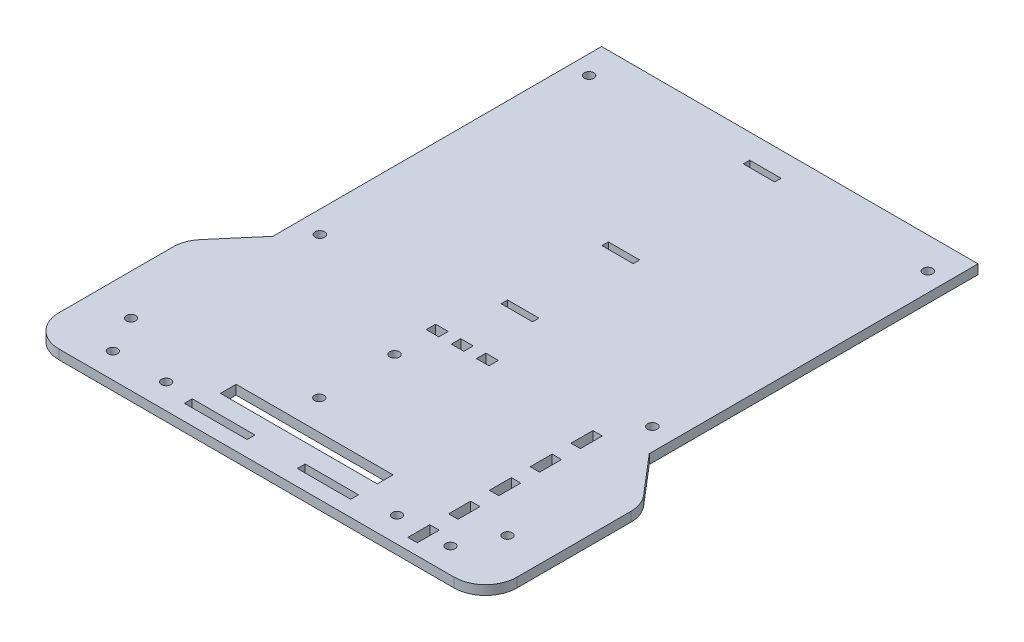
SolidWorks part; units mm, degrees
ref_plane "Front Plane" through (0, 0, 0) normal (0, 0, 1) x (1, 0, 0)
ref_plane "Top Plane" through (0, 0, 0) normal (0, 1, 0) x (1, 0, 0)
ref_plane "Right Plane" through (0, 0, 0) normal (1, 0, 0) x (0, 0, -1)
sketch "Sketch1" plane through (0, 0, 0) normal (0, 1, 0) x (1, 0, 0)
  line L0 (-73, -35) -> (-60, -19.8013)
  line L1 (60, -85) -> (-60, -85)
  line L2 (60, -19.8013) -> (60, 85)
  line L3 (60, 85) -> (-60, 85)
  line L4 (-60, -19.8013) -> (-60, 85)
  line L5 (60, -85) -> (-60, 85) construction
  line L6 (60, 85) -> (-60, -85) construction
  line L7 (0, 0) -> (0, -85) construction
  line L9 (-60, -85) -> (-73, -85)
  line L10 (-73, -35) -> (-73, -85)
  line L11 (60, -85) -> (73, -85)
  line L12 (73, -35) -> (73, -85)
  line L13 (73, -35) -> (60, -19.8013)
  point P0 (0, 0)
  dimension "D1" = 170
  dimension "D2" = 120
  dimension "D3" = 50
  dimension "D4" = 13
  dimension "D5" = 20
extrude "Boss-Extrude1" add sketch "Sketch1" along normal blind 3
sketch "Sketch2" plane through (0, 3, 0) normal (0, 1, 0) x (1, 0, 0)
  line L0 (0, 0) -> (0, 85) construction
  line L1 (60, 85) -> (-60, 85) construction
  line L2 (-60, 85) -> (-60, -19.8013) construction
  circle A0 centre (-53, -11.81) radius 1.525
  circle A1 centre (-54, 75) radius 1.525
  circle A2 centre (53, -11.81) radius 1.525
  circle A3 centre (54, 75) radius 1.525
  dimension "D1" = 10
  dimension "D2" = 3.05
  dimension "D3" = 6
  dimension "D4" = 3.05
  dimension "D5" = 7
  dimension "D6" = 86.81
extrude "Cut-Extrude1" cut sketch "Sketch2" against normal through all
sketch "Sketch3" plane through (0, 3, 0) normal (0, 1, 0) x (1, 0, 0)
  line L0 (-5, 32.14) -> (5, 32.14)
  line L1 (-5, 0.04) -> (5, 0.04)
  line L2 (-5, 0.04) -> (-5, -2.01)
  line L3 (-5, -2.01) -> (5, -2.01)
  line L4 (5, 0.04) -> (5, -2.01)
  line L5 (-5, 0.04) -> (5, -2.01) construction
  line L6 (-5, -2.01) -> (5, 0.04) construction
  line L7 (-5, 32.14) -> (-5, 30.09)
  line L8 (-5, 30.09) -> (5, 30.09)
  line L9 (5, 32.14) -> (5, 30.09)
  line L11 (-5, 77.24) -> (5, 77.24)
  line L12 (-5, 77.24) -> (-5, 75.19)
  line L13 (-5, 75.19) -> (5, 75.19)
  line L14 (-5, 64.24) -> (5, 64.24) [skipped]
  line L15 (-5, 64.24) -> (-5, 62.19) [skipped]
  line L16 (-5, 62.19) -> (5, 62.19) [skipped]
  line L17 (5, 64.24) -> (5, 62.19) [skipped]
  line L18 (5, 77.24) -> (5, 75.19)
  line L19 (-5, 77.24) -> (5, 75.19) construction
  line L20 (-5, 75.19) -> (5, 77.24) construction
  circle A0 centre (-53, -11.81) radius 1.525 construction
  point P0 (0, -0.985)
  point P8 (0, 76.215)
  dimension "D2" = 9.8
  dimension "D1" = 2.05
  dimension "D3" = 10
  dimension "D4" = 0
  dimension "D6" = 2.05
  dimension "D7" = 10
  dimension "D8" = 0
  dimension "D9" = 43.05
  dimension "D10" = 30.05
  dimension "D5" = 3
extrude "Cut-Extrude2" cut sketch "Sketch3" against normal through all
sketch "Sketch4" plane through (0, 3, 0) normal (0, 1, 0) x (1, 0, 0)
  line L0 (-73, -85) -> (73, -85) construction
  line L1 (-60, 85) -> (-60, -19.8013) construction
  line L2 (0, 0) -> (0, -85) construction
  circle A1 centre (-60, -65) radius 1.5
  circle A2 centre (-53.8153, -77) radius 1.5
  circle A3 centre (53.8153, -77) radius 1.5
  circle A4 centre (60, -65) radius 1.5
  dimension "D1" = 3
  dimension "D2" = 3
  dimension "D4" = 8
  dimension "D5" = 13.5
  dimension "D6" = 0
  dimension "D3" = 20
extrude "Cut-Extrude3" cut sketch "Sketch4" against normal blind 3
sketch "Sketch5" plane through (0, 3, 0) normal (0, 1, 0) x (1, 0, 0)
  line L0 (0, 0) -> (0, -85) construction
  line L2 (25, -71.5) -> (-25, -71.5)
  line L3 (25, -71.5) -> (25, -66.5)
  line L4 (25, -66.5) -> (-25, -66.5)
  line L5 (-25, -71.5) -> (-25, -66.5)
  line L6 (25, -71.5) -> (-25, -66.5) construction
  line L7 (-73, -85) -> (73, -85) construction
  line L8 (25, -66.5) -> (-25, -71.5) construction
  circle A0 centre (-36.8, -77) radius 1.5
  circle A1 centre (36.8, -77) radius 1.5
  point P0 (0, -69)
  dimension "D3" = 3
  dimension "D4" = 5.5
  dimension "D5" = 8
  dimension "D1" = 5
  dimension "D2" = 50
  dimension "D6" = 36.8
extrude "Cut-Extrude4" cut sketch "Sketch5" against normal blind 3
sketch "Sketch6" plane through (0, 3, 0) normal (0, 1, 0) x (1, 0, 0)
  line L0 (44.6365, -35.4032) -> (44.6365, -42.4032)
  line L7 (44.6365, -22.4032) -> (47.6365, -22.4032)
  line L8 (44.6365, -22.4032) -> (44.6365, -29.4032)
  line L9 (44.6365, -29.4032) -> (47.6365, -29.4032)
  line L10 (47.6365, -22.4032) -> (47.6365, -29.4032)
  line L11 (44.6365, -22.4032) -> (47.6365, -29.4032) construction
  line L12 (44.6365, -29.4032) -> (47.6365, -22.4032) construction
  line L13 (44.6365, -35.4032) -> (47.6365, -35.4032)
  line L14 (47.6365, -35.4032) -> (47.6365, -42.4032)
  line L15 (44.6365, -42.4032) -> (47.6365, -42.4032)
  line L16 (44.6365, -48.4032) -> (44.6365, -55.4032)
  line L17 (44.6365, -48.4032) -> (47.6365, -48.4032)
  line L18 (47.6365, -48.4032) -> (47.6365, -55.4032)
  line L19 (44.6365, -55.4032) -> (47.6365, -55.4032)
  line L20 (44.6365, -61.4032) -> (44.6365, -68.4032)
  line L21 (44.6365, -61.4032) -> (47.6365, -61.4032)
  line L22 (47.6365, -61.4032) -> (47.6365, -68.4032)
  line L23 (44.6365, -68.4032) -> (47.6365, -68.4032)
  line L24 (44.6365, -74.4032) -> (44.6365, -81.4032)
  line L25 (44.6365, -74.4032) -> (47.6365, -74.4032)
  line L26 (47.6365, -74.4032) -> (47.6365, -81.4032)
  line L27 (44.6365, -81.4032) -> (47.6365, -81.4032)
  line L29 (-9.793, -18.112) -> (-5.793, -18.112)
  line L30 (-9.793, -18.112) -> (-9.793, -21.112)
  line L31 (-9.793, -21.112) -> (-5.793, -21.112)
  line L32 (-5.793, -18.112) -> (-5.793, -21.112)
  line L33 (-9.793, -18.112) -> (-5.793, -21.112) construction
  line L34 (-9.793, -21.112) -> (-5.793, -18.112) construction
  line L35 (0.1365, -44.4032) -> (9.41, -44.4032) construction
  line L39 (-1.793, -18.1033) -> (2.207, -18.1033)
  line L40 (-1.793, -18.1033) -> (-1.793, -21.1033)
  line L41 (-1.793, -21.1033) -> (2.207, -21.1033)
  line L42 (2.207, -18.1033) -> (2.207, -21.1033)
  line L43 (-7.793, -19.612) -> (-7.793, -18.4227) construction
  line L44 (6.207, -18.1033) -> (10.207, -18.1033)
  line L45 (6.207, -18.1033) -> (6.207, -21.1033)
  line L46 (6.207, -21.1033) -> (10.207, -21.1033)
  line L47 (10.207, -18.1033) -> (10.207, -21.1033)
  point P0 (-7.793, -44.4032)
  point P9 (-7.793, -19.612)
  point P30 (-7.793, -44.4032)
  point P55 (-7.793, -44.4032)
extrude "Cut-Extrude5" cut sketch "Sketch6" against normal blind 10
sketch "Sketch7" plane through (0, 3, 0) normal (0, 1, 0) x (1, 0, 0)
  line L0 (-73, -35) -> (-73, -85) construction
  line L1 (-29.1759, -77.5) -> (-28, -77.5)
  line L2 (-73, -85) -> (73, -85) construction
  line L8 (0, -85) -> (0, -22.2641) construction
  line L9 (-8, -80) -> (-25, -80)
  line L10 (-8, -80) -> (-8, -77.5)
  line L11 (-8, -77.5) -> (-25, -77.5)
  line L16 (25, -80) -> (25, -77.5)
  line L17 (8, -80) -> (25, -80)
  line L18 (8, -80) -> (8, -77.5)
  line L19 (8, -77.5) -> (25, -77.5)
  line L21 (-25, -80) -> (-28, -80)
  line L23 (-25, -77.5) -> (-29.1759, -77.5)
  line L24 (-28, -80) -> (-28, -77.5)
  circle A0 centre (-68, -57) radius 1.5
  circle A1 centre (-8, -57) radius 1.5
  circle A2 centre (-8, -33) radius 1.5
  point P10 (-19, -78.75)
  dimension "D1" = 3
  dimension "D2" = 2.5
  dimension "D3" = 3
  dimension "D7" = 8
  dimension "D10" = 28
  dimension "D12" = 28
  dimension "D4" = 20
  dimension "D5" = 5
  dimension "D6" = 28
  dimension "D8" = 24
  dimension "D9" = 5
  dimension "D11" = 60
  dimension "D14" = 5
  dimension "D15" = 2.5
extrude "Cut-Extrude6" cut sketch "Sketch7" against normal blind 10 contours L24 L21 L9 L10 L11 L23 L1 | L19 L18 L17 L16 | A1 | A2 region at (-18, 3, 78.75) region at (16.5, 3, 78.75)
fillet "Fillet3" radius 10 4 edges at (-73, 1.5, 35) (73, 1.5, 35) (73, 1.5, 85) (-73, 1.5, 85)
